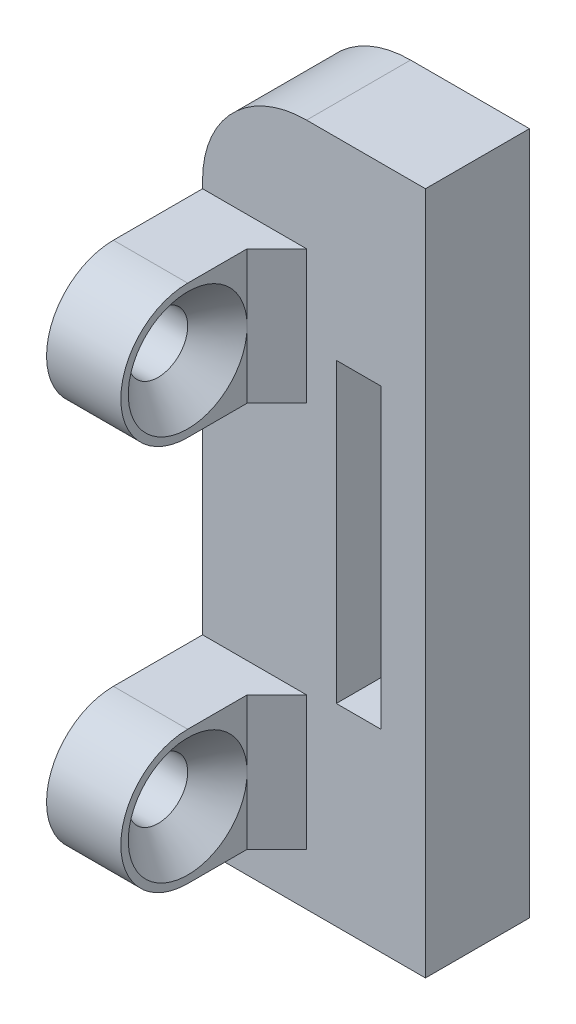
SolidWorks part; units mm, degrees
ref_plane "Front Plane" through (0, 0, 0) normal (0, 0, 1) x (1, 0, 0)
ref_plane "Top Plane" through (0, 0, 0) normal (0, 1, 0) x (1, 0, 0)
ref_plane "Right Plane" through (0, 0, 0) normal (1, 0, 0) x (0, 0, -1)
sketch "Sketch1" plane through (0, 0, 0) normal (0, 0, 1) x (1, 0, 0)
  line L0 (22, 21) -> (14, 21)
  line L1 (7, 14) -> (7, -25)
  line L2 (7, -25) -> (22, -25)
  line L3 (22, -25) -> (22, 21)
  arc A0 (14, 21) -> (7, 14) centre (14, 14) ccw
extrude "Boss-Extrude1" add sketch "Sketch1" along normal blind 7
sketch "Sketch2" plane through (7, 0, 0) normal (-1, 0, 0) x (0, 0, 1)
  line L0 (7, 13.5) -> (13, 13.5)
  line L1 (7, 14) -> (7, -25) construction
  line L3 (7, 4.5) -> (13, 4.5)
  line L4 (7, 13.5) -> (7, 4.5)
  line L9 (13, 9) -> (15, 9) construction
  arc A0 (13, 13.5) -> (13, 4.5) centre (13, 9) cw
  arc A3 (15, 7) -> (15, 11) centre (15, 9) ccw construction
  circle A4 centre (13, 9) radius 2
  dimension "D3" = 4
  dimension "D1" = 9
  dimension "D2" = 6
extrude "Boss-Extrude2" add sketch "Sketch2" against normal blind 5
ref_plane "Plane1" through (0, -4, 0) normal (0, 1, 0) x (1, 0, 0)
mirror "Mirror1" about plane through (0, -4, 0) normal (0, 1, 0) of "Boss-Extrude2"
chamfer "Chamfer1" distance 2 angle 45 2 edges at (12, -15, 13) (12, 7, 13)
chamfer "Chamfer2" distance 2 angle 45 2 edges at (12, -17, 7) (12, 9, 7)
sketch "Sketch3" plane through (0, 0, 0) normal (0, 0, -1) x (-1, 0, 0)
  line L0 (-22, -25) -> (-22, 21) construction
  line L1 (-19, -12) -> (-16, -12)
  line L2 (-19, -12) -> (-19, 8)
  line L3 (-19, 8) -> (-16, 8)
  line L4 (-16, -12) -> (-16, 8)
  line L5 (-19, -2) -> (-22, -2) construction
  dimension "D1" = 3
  dimension "D2" = 20
  dimension "D3" = 3
extrude "Cut-Extrude1" cut sketch "Sketch3" against normal through all
